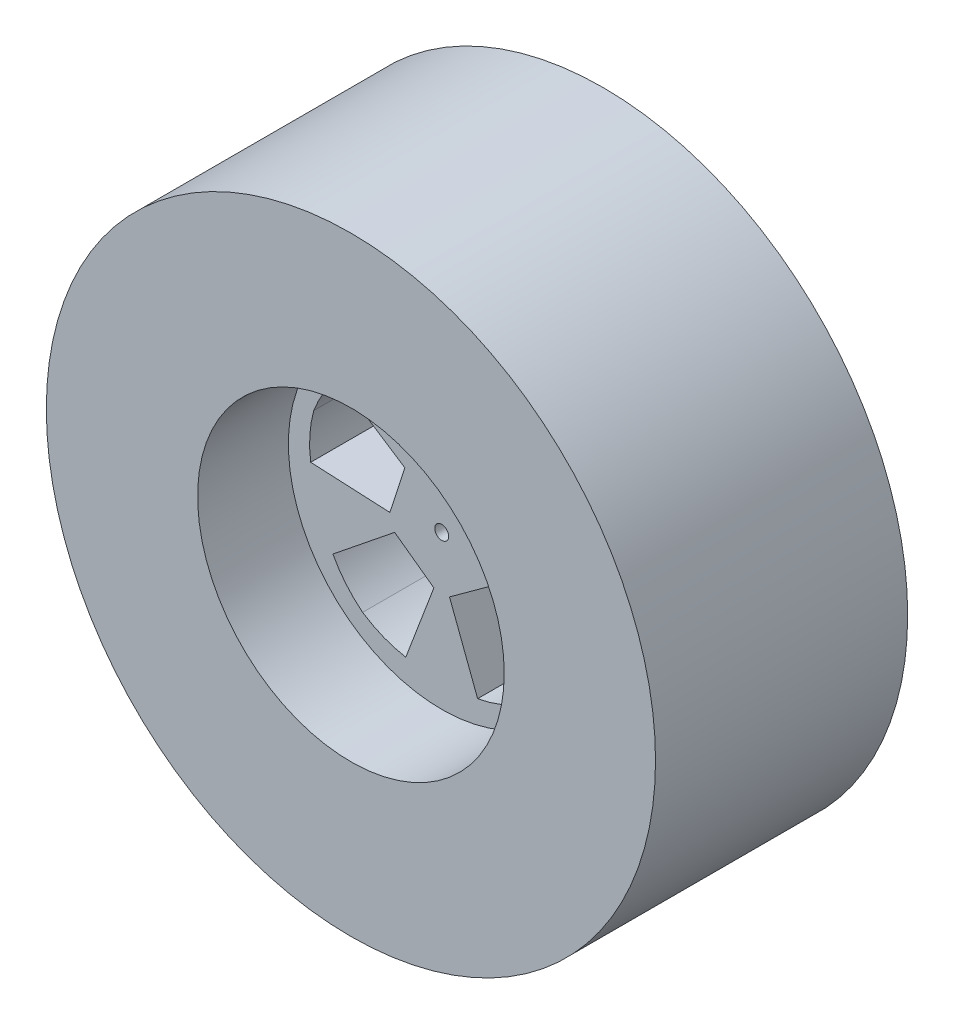
SolidWorks part; units mm, degrees
ref_plane "Front Plane" through (0, 0, 0) normal (0, 0, 1) x (1, 0, 0)
ref_plane "Top Plane" through (0, 0, 0) normal (0, 1, 0) x (1, 0, 0)
ref_plane "Right Plane" through (0, 0, 0) normal (1, 0, 0) x (0, 0, -1)
sketch "Sketch1" plane through (0, 0, 0) normal (0, 0, 1) x (1, 0, 0)
  line L0 (48.0589, 92.4823) -> (-48.0589, 92.4823)
  line L1 (-48.0589, 92.4823) -> (-89.2857, 244.1155)
  line L2 (0, 604) -> (0, 92.4823) construction
  line L3 (48.0589, 92.4823) -> (89.2857, 244.1155)
  line L16 (-73.1049, 74.2854) -> (-204.5768, 160.3516) [skipped]
  line L17 (-102.8069, -17.1282) -> (-259.7584, -9.4799) [skipped]
  line L18 (-73.1049, 74.2854) -> (-102.8069, -17.1282) [skipped]
  line L19 (-93.2402, -46.5714) -> (-215.7211, -145.0128) [skipped]
  line L20 (-15.4792, -103.0681) -> (-71.2538, -249.9744) [skipped]
  line L21 (0, -304) -> (0, -604) construction
  line L22 (-93.2402, -46.5714) -> (-15.4792, -103.0681) [skipped]
  line L23 (15.4792, -103.0681) -> (71.2538, -249.9744) [skipped]
  line L24 (93.2402, -46.5714) -> (215.7211, -145.0128) [skipped]
  line L25 (102.8069, -17.1282) -> (259.7584, -9.4799) [skipped]
  line L26 (102.8069, -17.1282) -> (73.1049, 74.2854) [skipped]
  line L27 (15.4792, -103.0681) -> (93.2402, -46.5714) [skipped]
  line L28 (73.1049, 74.2854) -> (204.5768, 160.3516) [skipped]
  line L29 (102.8069, -17.1282) -> (73.1049, 74.2854)
  line L30 (73.1049, 74.2854) -> (204.5768, 160.3516)
  line L31 (102.8069, -17.1282) -> (259.7584, -9.4799)
  line L32 (15.4792, -103.0681) -> (93.2402, -46.5714)
  line L33 (93.2402, -46.5714) -> (215.7211, -145.0128)
  line L34 (15.4792, -103.0681) -> (71.2538, -249.9744)
  line L35 (-93.2402, -46.5714) -> (-15.4792, -103.0681)
  line L36 (-15.4792, -103.0681) -> (-71.2538, -249.9744)
  line L37 (-93.2402, -46.5714) -> (-215.7211, -145.0128)
  line L38 (-73.1049, 74.2854) -> (-102.8069, -17.1282)
  line L39 (-102.8069, -17.1282) -> (-259.7584, -9.4799)
  line L40 (-73.1049, 74.2854) -> (-204.5768, 160.3516)
  arc A0 (-110.9053, -283.0477) -> (110.9053, -283.0477) centre (0, 0) ccw
  circle A1 centre (0, 0) radius 604
  arc A2 (256.0955, 163.802) -> (-256.0955, 163.802) centre (0, 0) ccw
  circle A3 centre (0, 0) radius 304
  spline S0 degree 2 poles (-89.2857, 244.1155) (-47.2089, 264.6202) (0, 266.7058) knots 0 0 0 1 1 1
  spline S1 degree 2 poles (89.2857, 244.1155) (47.2089, 264.6202) (0, 266.7058) knots 0 0 0 1 1 1
  spline S2 degree 2 poles (204.5768, 160.3516) (237.0804, 126.6704) (253.6523, 82.4166) knots 0 0 0 1 1 1
  spline S3 degree 2 poles (259.7584, -9.4799) (266.2571, 36.8738) (253.6523, 82.4166) knots 0 0 0 1 1 1
  spline S4 degree 2 poles (215.7211, -145.0128) (193.7326, -186.3335) (156.7658, -215.7696) knots 0 0 0 1 1 1
  spline S6 degree 2 poles (71.2538, -249.9744) (117.347, -241.8309) (156.7658, -215.7696) knots 0 0 0 1 1 1
  spline S7 degree 2 poles (-71.2538, -249.9744) (-117.347, -241.8309) (-156.7658, -215.7696) knots 0 0 0 1 1 1
  spline S8 degree 2 poles (-215.7211, -145.0128) (-193.7326, -186.3335) (-156.7658, -215.7696) knots 0 0 0 1 1 1
  spline S9 degree 2 poles (-259.7584, -9.4799) (-266.2571, 36.8738) (-253.6523, 82.4166) knots 0 0 0 1 1 1
  spline S10 degree 2 poles (-204.5768, 160.3516) (-237.0804, 126.6704) (-253.6523, 82.4166) knots 0 0 0 1 1 1
  point P12 (0, 92.4823)
  dimension "D1" = 1208
  dimension "D2" = 300
  dimension "D3" = 5
  dimension "D4" = 5
extrude "Boss-Extrude1" add sketch "Sketch1" along normal blind 250 and the other way blind 250 contours L2 A1 A0 | A1 L2 A0 region at (415.0125, 415.0125, 0)
extrude "Boss-Extrude2" add sketch "Sketch1<3>" along normal blind 70 and the other way blind 70 contours A0 L2 S1 L3 L0 L30 | L2 A0 L0 L1 S0 S7 region at (0, 0, 0)
sketch "Sketch1<3>" plane through (0, 0, 0) normal (0, 0, 1) x (1, 0, 0) same geometry as "Sketch1"
sketch "Sketch2" plane through (0, 0, 0) normal (0, 0, 1) x (1, 0, 0)
  circle A0 centre (0, 0) radius 13.799
extrude "Cut-Extrude1" cut sketch "Sketch2" along normal through all and the other way blind 80 contours A0 region at (0, 0, 0)
